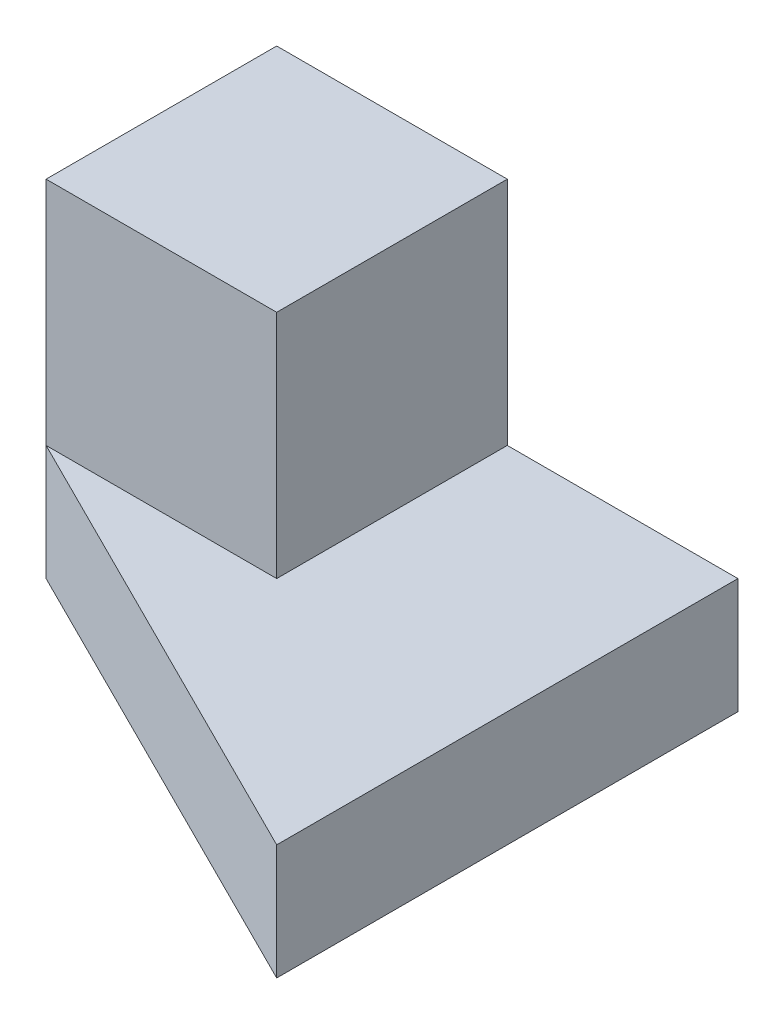
SolidWorks part; units mm, degrees
ref_plane "前基準面" through (0, 0, 0) normal (0, 0, 1) x (1, 0, 0)
ref_plane "上基準面" through (0, 0, 0) normal (0, 1, 0) x (1, 0, 0)
ref_plane "右基準面" through (0, 0, 0) normal (1, 0, 0) x (0, 0, -1)
sketch "草圖1" plane through (0, 0, 0) normal (0, 1, 0) x (1, 0, 0)
  line L0 (0, 0) -> (0, 18.1677) construction
  line L1 (0, 0) -> (0, 2)
  line L2 (0, 2) -> (4, 2)
  line L3 (4, 2) -> (4, -2)
  line L4 (4, -2) -> (0, 0)
  line L5 (2, 2) -> (2, 0)
  line L6 (2, 0) -> (0, 0)
  dimension "D1" = 4
  dimension "D2" = 2
  dimension "D3" = 4
  dimension "D4" = 2
  dimension "D5" = 2
extrude "填料-伸長1" add sketch "草圖1" along normal blind 3 contours L6 L5 L2 L1 region at (1, 0, -1)
extrude "填料-伸長2" add sketch "草圖1<3>" along normal blind 1 contours L5 L6 L4 L3 L2 region at (2.8333, 0, -0.1667)
sketch "草圖1<3>" plane through (0, 0, 0) normal (0, 1, 0) x (1, 0, 0) same geometry as "草圖1"
